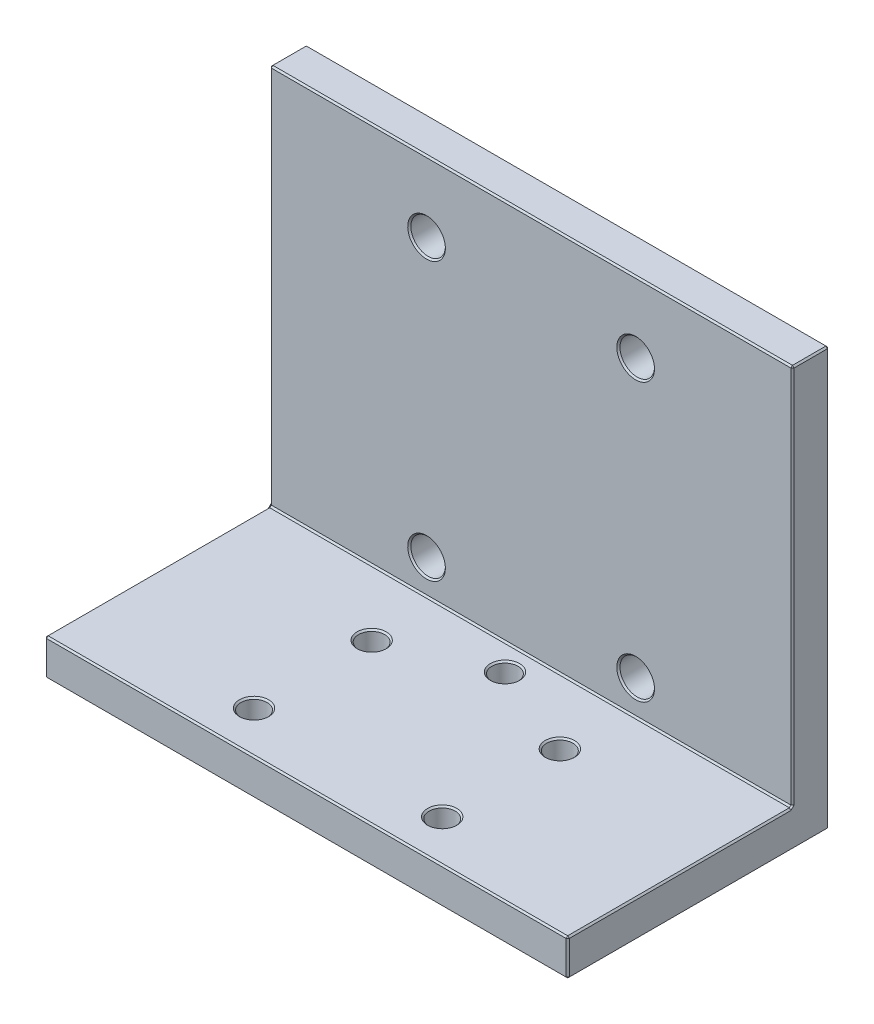
SolidWorks part; units mm, degrees
material "1060 Alloy"
ref_plane "Front Plane" through (0, 0, 0) normal (0, 0, 1) x (1, 0, 0)
ref_plane "Top Plane" through (0, 0, 0) normal (0, 1, 0) x (1, 0, 0)
ref_plane "Right Plane" through (0, 0, 0) normal (1, 0, 0) x (0, 0, -1)
sketch "Sketch1" plane through (0, 0, 0) normal (1, 0, 0) x (0, 0, -1)
  line L2 (0, 0) -> (0, 80)
  line L3 (0, 80) -> (-7, 80)
  line L4 (-7, 7) -> (-7, 80)
  line L5 (0, 0) -> (-50, 0)
  line L7 (-7, 7) -> (-50, 7)
  line L8 (-50, 0) -> (-50, 7)
  dimension "D2" = 80
  dimension "D3" = 50
extrude "Boss-Extrude1" add sketch "Sketch1" along normal mid plane 100
sketch "Sketch2" plane through (0, 0, 7) normal (0, 0, 1) x (1, 0, 0)
  line L0 (50, 0) -> (-50, 0) construction
  line L1 (20, 13.5) -> (-20, 13.5) construction
  line L2 (20, 13.5) -> (20, 66.5) construction
  line L3 (20, 66.5) -> (-20, 66.5) construction
  line L4 (-20, 13.5) -> (-20, 66.5) construction
  line L5 (20, 13.5) -> (-20, 66.5) construction
  line L6 (20, 66.5) -> (-20, 13.5) construction
  line L7 (50, 80) -> (50, 7) construction
  line L8 (0, 40) -> (0, 0) construction
  line L9 (-50, 80) -> (50, 80) construction
  line L10 (-50, 80) -> (-50, 0) construction
  line L11 (-50, 0) -> (50, 0) construction
  line L12 (50, 80) -> (50, 0) construction
  line L13 (-50, 80) -> (-50, 7) construction
  circle A0 centre (-20, 66.5) radius 3.3
  circle A1 centre (20, 66.5) radius 3.3
  circle A2 centre (20, 13.5) radius 3.3
  circle A3 centre (-20, 13.5) radius 3.3
  point P0 (0, 40)
  dimension "D1" = 6.6
  dimension "D2" = 40
  dimension "D3" = 53
  dimension "D5" = 80
  dimension "D4" = 40
extrude "Cut-Extrude1" cut sketch "Sketch2" against normal blind 100
sketch "Sketch3" plane through (0, 7, 0) normal (0, 1, 0) x (1, 0, 0)
  line L0 (0, 0) -> (0, -30.75) construction
  line L1 (18, -19.5) -> (-18, -19.5) construction
  line L2 (18, -19.5) -> (18, -42) construction
  line L3 (18, -42) -> (-18, -42) construction
  line L4 (-18, -19.5) -> (-18, -42) construction
  line L5 (18, -19.5) -> (-18, -42) construction
  line L6 (18, -42) -> (-18, -19.5) construction
  line L9 (50, 0) -> (-50, 0) construction
  circle A0 centre (-18, -19.5) radius 2.5
  circle A1 centre (-18, -42) radius 2.5
  circle A2 centre (18, -42) radius 2.5
  circle A3 centre (18, -19.5) radius 2.5
  circle A4 centre (0, -12) radius 2.5
  point P0 (0, -30.75)
  dimension "D1" = 5
  dimension "D2" = 22.5
  dimension "D3" = 36
  dimension "D4" = 7.5
  dimension "D5" = 12
extrude "Cut-Extrude2" cut sketch "Sketch3" against normal blind 100
chamfer "Chamfer1" distance 0.3 angle 45 36 edges at (-18, 7, 22) (-18, 7, 44.5) (18, 7, 44.5) (18, 7, 22) (0, 7, 14.5) (-16.7, 66.5, 7) (23.3, 66.5, 7) (23.3, 13.5, 7) (-16.7, 13.5, 7) (50, 7, 28.5) (0, 7, 50) (-50, 7, 28.5) (0, 80, 7) (50, 43.5, 7) (0, 7, 7) (-50, 43.5, 7) (0, 0, 0) (0, 80, 0) (50, 3.5, 50) (50, 80, 3.5) (50, 40, 0) (50, 0, 25) (0, 0, 50) (-50, 3.5, 50) (-50, 80, 3.5) (-50, 40, 0) (-50, 0, 25) (-16.7, 66.5, 0) (23.3, 66.5, 0) (23.3, 13.5, 0) (-16.7, 13.5, 0) (-18, 0, 22) (-18, 0, 44.5) (18, 0, 44.5) (18, 0, 22) (0, 0, 14.5)
equation "\"M5_tap\"=4.2mm       ' Below you can do mesurements as follows: cm, mm, ft, in, m, "
equation "\"M5_clearence\"=5.5mm"
equation "\"M6_tap\"=5mm"
equation "\"M6_clearence\"=6.6mm"
equation "\"D1@Sketch2\"=\"M6_clearence\""
equation "\"D1@Sketch3\"=\"M6_tap\""
equation "\"work_area_width\"=1100mm"
equation "\"work_area_depth\"=900mm"
equation "\"steel_base_width\"=80mm"
equation "\"steel_base_height\"=50mm"
equation "\"steel_base_wall_thickness\"=3mm"
equation "\"steel_base_radius\"=6mm"
equation "\"steel_sides_width\"=80mm    'this tube is rotated so flip width/height"
equation "\"steel_sides_height\"=50mm    'this tube is rotated so flip width/height"
equation "\"steel_sides_wall_thickness\"=3mm"
equation "\"steel_sides_radius\"=6mm"
equation "\"steel_gantry_width\"=80mm    'this tube is rotated so flip width/height"
equation "\"steel_gantry_height\"=50mm    'this tube is rotated so flip width/height"
equation "\"steel_gantry_wall_thickness\"=3mm"
equation "\"steel_gantry_radius\"=6mm"
equation "\"steel_rollers_width\"=80mm"
equation "\"steel_rollers_height\"=50mm    'keep as low as possible as this increases how big plastic parts are"
equation "\"steel_rollers_wall_thickness\"=3mm"
equation "\"steel_rollers_radius\"=6mm"
equation "\"steel_zbox_width\"=80mm     'if the gantry height (rotated) is too thick, a wider zbox is necessary"
equation "\"steel_zbox_height\"=50mm    'hole patteren changes as the zbox and gantry height (rotated) changes."
equation "\"steel_zbox_wall_thickness\"=3mm"
equation "\"steel_zbox_radius\"=6mm"
equation "\"alu_zangle_width\"=80mm     'check that it doesn't interfer with the gantry"
equation "\"alu_zangle_height\"=50mm"
equation "\"alu_zangle_wall_thickness\"=7mm  'check that it doesn't interfer with the gantry"
equation "\"D1@Sketch1\"=\"alu_zangle_wall_thickness\""
equation "\"D2@Sketch1\"=\"alu_zangle_width\""
equation "\"D3@Sketch1\"=\"alu_zangle_height\""
equation "\"D5@Sketch2\"=\"steel_zbox_width\""
equation "\"D5@Sketch3\"=\"alu_zangle_wall_thickness\"+5"
equation "\"D4@Sketch2\"=\"steel_zbox_width\"/2"
